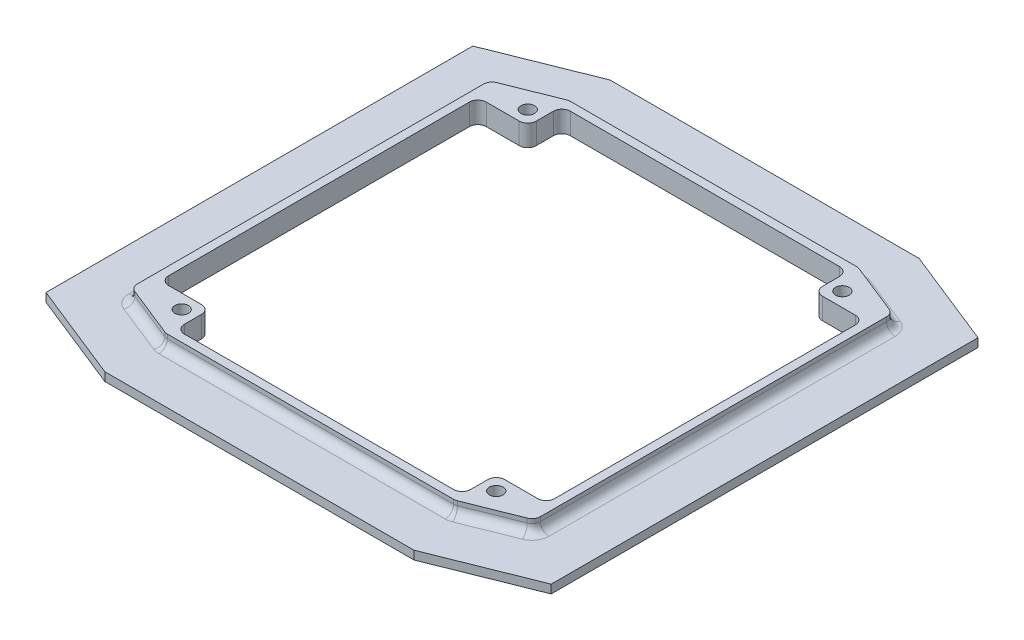
SolidWorks part; units mm, degrees
ref_plane "Front Plane" through (0, 0, 0) normal (0, 0, 1) x (1, 0, 0)
ref_plane "Top Plane" through (0, 0, 0) normal (0, 1, 0) x (1, 0, 0)
ref_plane "Right Plane" through (0, 0, 0) normal (1, 0, 0) x (0, 0, -1)
sketch "Sketch1" plane through (0, 0, 0) normal (0, 1, 0) x (1, 0, 0)
  line L5 (-35.5, 0) -> (0, 0) construction
  line L6 (-25.5, -35.5) -> (25.5, -35.5)
  line L10 (-35.5, -31.5) -> (-35.5, 31.5)
  line L11 (-25.5, 35.5) -> (25.5, 35.5)
  line L12 (35.5, -31.5) -> (35.5, 31.5)
  line L13 (0, 0) -> (0, 35.5) construction
  line L14 (25.5, -35.5) -> (35.5, -31.5)
  line L15 (25.5, 35.5) -> (35.5, 31.5)
  line L16 (-25.5, -35.5) -> (-35.5, -31.5)
  line L17 (-25.5, 35.5) -> (-35.5, 31.5)
  point P0 (0, 0)
  point P4 (35.5, -35.5)
  dimension "D3" = 4
  dimension "D2" = 10
  dimension "D4" = 71
extrude "Boss-Extrude1" add sketch "Sketch1" along normal mid plane 4.5
sketch "Sketch2" plane through (0, 2.25, 0) normal (0, 1, 0) x (1, 0, 0)
  line L16 (27.2332, -44.5) -> (44.5, -37.5933)
  line L17 (44.5, -37.5933) -> (44.5, 37.5933)
  line L18 (44.5, 37.5933) -> (27.2332, 44.5)
  line L19 (27.2332, 44.5) -> (-27.2332, 44.5)
  line L20 (-27.2332, 44.5) -> (-44.5, 37.5933)
  line L21 (-44.5, 37.5933) -> (-44.5, -37.5933)
  line L22 (-44.5, -37.5933) -> (-27.2332, -44.5)
  line L23 (-27.2332, -44.5) -> (27.2332, -44.5)
  line L24 (27.2332, -44.5) -> (44.5, -37.5933)
  line L25 (44.5, -37.5933) -> (44.5, 37.5933)
  line L26 (44.5, 37.5933) -> (27.2332, 44.5)
  line L27 (27.2332, 44.5) -> (-27.2332, 44.5)
  line L28 (-27.2332, 44.5) -> (-44.5, 37.5933)
  line L29 (-44.5, 37.5933) -> (-44.5, -37.5933)
  line L30 (-44.5, -37.5933) -> (-27.2332, -44.5)
  line L31 (-27.2332, -44.5) -> (27.2332, -44.5)
  dimension "D1" = 9
extrude "Boss-Extrude2" add sketch "Sketch2" along normal blind 1.5
mirror "Mirror1" about plane through (0, 0, 0) normal (0, 1, 0) of "Boss-Extrude2"
sketch "Sketch3" plane through (0, 0, 0) normal (0, 1, 0) x (1, 0, 0)
  line L16 (-25.2111, -34) -> (25.2111, -34)
  line L17 (25.2111, -34) -> (34, -30.4845)
  line L18 (34, -30.4845) -> (34, 30.4845)
  line L19 (34, 30.4845) -> (25.2111, 34)
  line L20 (25.2111, 34) -> (-25.2111, 34)
  line L21 (-25.2111, 34) -> (-34, 30.4845)
  line L22 (-34, 30.4845) -> (-34, -30.4845)
  line L23 (-34, -30.4845) -> (-25.2111, -34)
  line L24 (-25.2111, -34) -> (25.2111, -34)
  line L25 (25.2111, -34) -> (34, -30.4845)
  line L26 (34, -30.4845) -> (34, 30.4845)
  line L27 (34, 30.4845) -> (25.2111, 34)
  line L28 (25.2111, 34) -> (-25.2111, 34)
  line L29 (-25.2111, 34) -> (-34, 30.4845)
  line L30 (-34, 30.4845) -> (-34, -30.4845)
  line L31 (-34, -30.4845) -> (-25.2111, -34)
  dimension "D1" = 10.5
extrude "Cut-Extrude1" cut sketch "Sketch3" against normal through all both and the other way through all
sketch "Sketch5" plane through (0, 0, 0) normal (0, 0, 1) x (1, 0, 0)
  line L0 (0, 0) -> (0, 28.4264) construction
  line L1 (-27.2332, 3.75) -> (27.2332, 3.75) construction
  line L2 (-26, 3.75) -> (-18, 3.75)
  line L3 (-26, 3.75) -> (-26, 16.55)
  line L4 (-26, 16.55) -> (-18, 16.55)
  line L5 (-18, 3.75) -> (-18, 16.55)
  line L6 (-22, 16.55) -> (-22, 9.7096) construction
  line L7 (18, 3.75) -> (18, 16.55)
  line L8 (26, 16.55) -> (18, 16.55)
  line L9 (26, 3.75) -> (26, 16.55)
  line L10 (26, 3.75) -> (18, 3.75)
  dimension "D1" = 22
  dimension "D3" = 12.8
  dimension "D2" = 8
extrude "Boss-Extrude3" add sketch "Sketch5" against normal blind 1.5 from surface starting at face at (0, 3, 44.5)
extrude "Boss-Extrude4" add sketch "Sketch5<2>" along normal blind 1.5 from surface starting at face at (0, 3, -44.5)
sketch "Sketch5<2>" plane through (0, 0, 0) normal (0, 0, 1) x (1, 0, 0) same geometry as "Sketch5"
sketch "Sketch6" plane through (0, 0, 0) normal (0, 0, 1) x (1, 0, 0)
  line L0 (-22, 16.55) -> (-22, 13.85) construction
  line L1 (-18, 16.55) -> (-26, 16.55) construction
  line L2 (0, 0) -> (0, 25.5714) construction
  line L3 (-22, 13.85) -> (-22, 8.45) construction
  circle A0 centre (-22, 13.85) radius 1.2
  circle A1 centre (22, 13.85) radius 1.2
  circle A2 centre (-22, 8.45) radius 1.2
  circle A3 centre (22, 8.45) radius 1.2
  dimension "D1" = 2.4
  dimension "D2" = 2.7
  dimension "D3" = 5.4
extrude "Cut-Extrude3" cut sketch "Sketch6" against normal through all both and the other way through all
fillet "Fillet1" radius 1.5 35 edges at (35.5, 0, 31.5) (25.5, 0, 35.5) (0, 2.25, -35.5) (0, -2.25, -35.5) (35.5, 2.25, 0) (35.5, -2.25, 0) (-35.5, 2.25, 0) (-35.5, -2.25, 0) (0, 2.25, 35.5) (0, -2.25, 35.5) (-25.5, 0, -35.5) (-30.5, 2.25, -33.5) (-35.5, 0, -31.5) (-30.5, -2.25, -33.5) (35.5, 0, -31.5) (30.5, 2.25, -33.5) (25.5, 0, -35.5) (30.5, -2.25, -33.5) (30.5, 2.25, 33.5) (30.5, -2.25, 33.5) (-35.5, 0, 31.5) (-30.5, 2.25, 33.5) (-25.5, 0, 35.5) (-30.5, -2.25, 33.5) (-22, 3.75, -43) (22, 3.75, -43) (-22, 3.75, 43) (22, 3.75, 43) (26, 3.75, 43.75) (-18, 3.75, 43.75) (18, 3.75, 43.75) (-26, 3.75, 43.75) (18, 3.75, -43.75) (26, 3.75, -43.75) (-26, 3.75, -43.75)
sketch "Sketch7" plane through (0, 0, 0) normal (0, 1, 0) x (1, 0, 0)
  line L0 (16.5, 44.5) -> (-18, 44.5) construction
  line L1 (44.5, -44.5) -> (-44.5, -44.5)
  line L2 (44.5, -44.5) -> (44.5, 44.5)
  line L3 (44.5, 44.5) -> (-44.5, 44.5)
  line L4 (-44.5, -44.5) -> (-44.5, 44.5)
  line L5 (44.5, -44.5) -> (-44.5, 44.5) construction
  line L6 (44.5, 44.5) -> (-44.5, -44.5) construction
  line L7 (-44.5, 37.5933) -> (-44.5, -37.5933) construction
  point P0 (0, 0)
extrude "Cut-Extrude4" cut sketch "Sketch7" along normal through all
sketch "Sketch8" plane through (0, 0, 0) normal (0, 1, 0) x (1, 0, 0)
  line L0 (34, 30.4845) -> (25.2111, 34)
  line L1 (34, 30.4845) -> (34, 27.9845)
  line L2 (34, 30.4845) -> (34, -30.4845) construction
  line L3 (34, 27.9845) -> (25.2111, 27.9845)
  line L4 (25.2111, 27.9845) -> (25.2111, 34)
  line L5 (44.5, 0) -> (-44.5, 0) construction
  line L6 (-44.5, 37.5933) -> (-44.5, -37.5933) construction
  line L7 (0, -44.5) -> (0, 44.5) construction
  line L8 (27.2332, 44.5) -> (-27.2332, 44.5) construction
  line L9 (34, 30.4845) -> (25.2111, 30.4845) construction
  line L10 (-34, 30.4845) -> (-25.2111, 30.4845) construction
  line L11 (-25.2111, 27.9845) -> (-25.2111, 34)
  line L12 (-34, 27.9845) -> (-25.2111, 27.9845)
  line L13 (-34, 30.4845) -> (-34, 27.9845)
  line L14 (-34, 30.4845) -> (-25.2111, 34)
  line L15 (34, -30.4845) -> (25.2111, -30.4845) construction
  line L16 (25.2111, -27.9845) -> (25.2111, -34)
  line L17 (34, -27.9845) -> (25.2111, -27.9845)
  line L18 (34, -30.4845) -> (34, -27.9845)
  line L19 (34, -30.4845) -> (25.2111, -34)
  line L20 (-34, -30.4845) -> (-25.2111, -30.4845) construction
  line L21 (-34, -30.4845) -> (-25.2111, -34)
  line L22 (-34, -30.4845) -> (-34, -27.9845)
  line L23 (-34, -27.9845) -> (-25.2111, -27.9845)
  line L24 (-25.2111, -27.9845) -> (-25.2111, -34)
  circle A0 centre (27.7111, 30.4845) radius 1.2
  circle A1 centre (-27.7111, 30.4845) radius 1.2
  circle A2 centre (27.7111, -30.4845) radius 1.2
  circle A3 centre (-27.7111, -30.4845) radius 1.2
  point P14 (0, 0)
  point P20 (0, 0)
  point P22 (28.0152, 30.4845)
  dimension "D2" = 2.4
  dimension "D1" = 2.5
  dimension "D3" = 2.5
extrude "Boss-Extrude5" add sketch "Sketch8" against normal up to surface (3.75 mm away) up to face at (0, -3.75, 0)
fillet "Fillet2" radius 1.5 12 edges at (25.2111, -1.875, -34) (25.2111, -1.875, -27.9845) (34, -1.875, -27.9845) (-34, -1.875, -27.9845) (-25.2111, -1.875, -27.9845) (-25.2111, -1.875, -34) (-34, -1.875, 27.9845) (-25.2111, -1.875, 27.9845) (-25.2111, -1.875, 34) (34, -1.875, 27.9845) (25.2111, -1.875, 27.9845) (25.2111, -1.875, 34)
